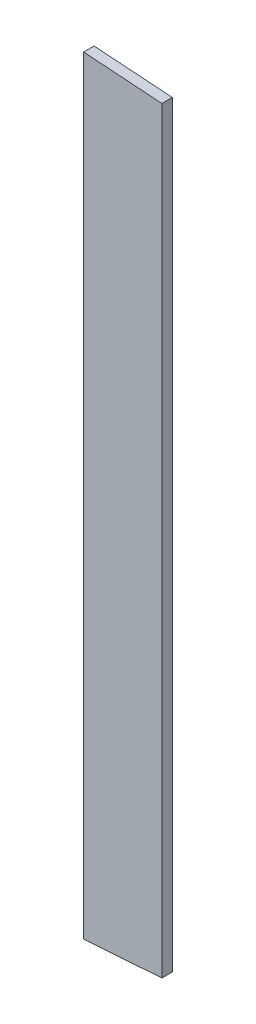
SolidWorks part; units mm, degrees
ref_plane "Front Plane" through (0, 0, 0) normal (0, 0, 1) x (1, 0, 0)
ref_plane "Top Plane" through (0, 0, 0) normal (0, 1, 0) x (1, 0, 0)
ref_plane "Right Plane" through (0, 0, 0) normal (1, 0, 0) x (0, 0, -1)
sketch "Sketch1" plane through (0, 0, 3895.25) normal (0, 0, 1) x (1, 0, 0)
  line L0 (-49.7697, 346.1083) -> (-64.7697, 345.0594)
  line L1 (-140.9262, 339.734) -> (58.5866, 353.6853) construction
  line L2 (-64.7697, 345.0594) -> (-64.7697, 492.4158)
  line L3 (58.5866, 483.7899) -> (-140.9262, 497.7412) construction
  line L4 (-64.7697, 492.4158) -> (-49.7697, 491.3669)
  line L5 (-49.7697, 491.3669) -> (-49.7697, 346.1083)
  dimension "D1" = 15
extrude "Boss-Extrude1" add sketch "Sketch1" along normal blind 2
ref_plane "Plane1" through (-57.2697, 0, 0) normal (1, 0, 0) x (0, 0, -1)
